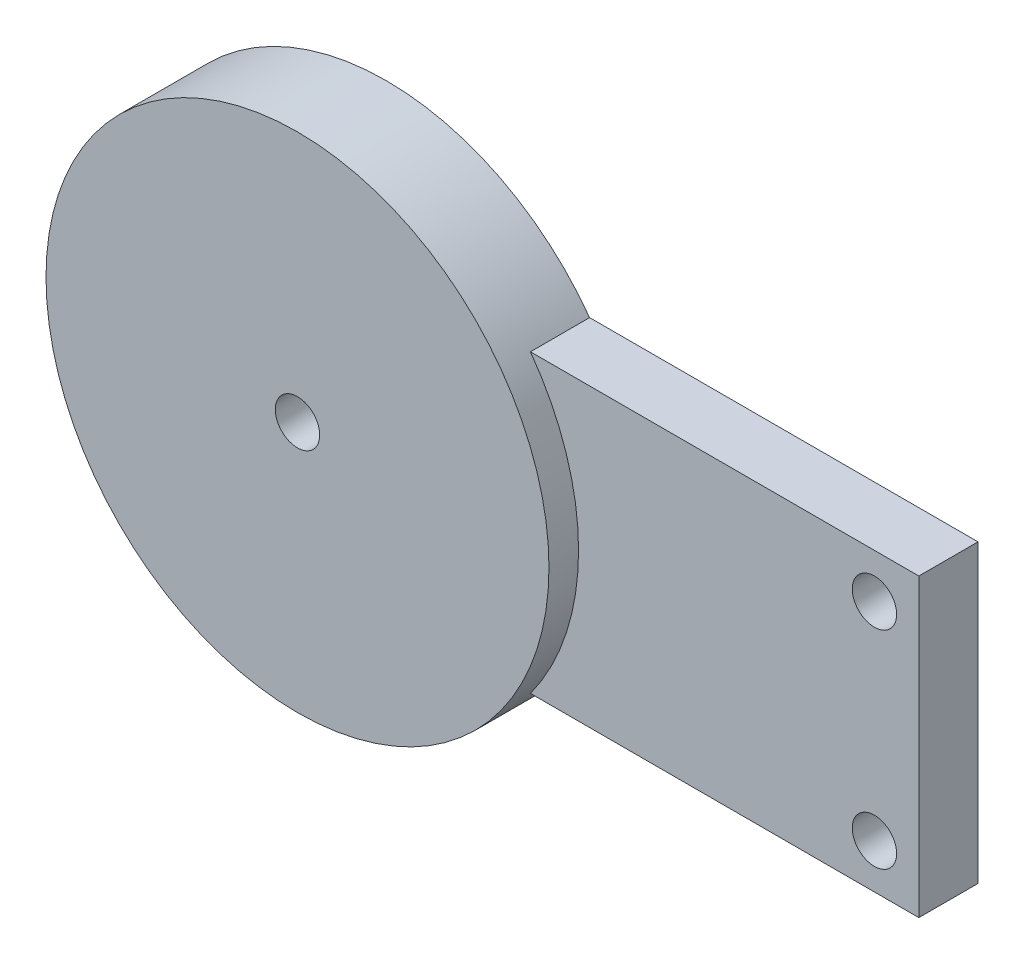
SolidWorks part; units mm, degrees
ref_plane "Plano frontal" through (0, 0, 0) normal (0, 0, 1) x (1, 0, 0)
ref_plane "Plano superior" through (0, 0, 0) normal (0, 1, 0) x (1, 0, 0)
ref_plane "Plano direito" through (0, 0, 0) normal (1, 0, 0) x (0, 0, -1)
sketch "Sketch1" plane through (0, 0, 0) normal (0, 0, 1) x (1, 0, 0)
  line L1 (-20, -10) -> (20, -10)
  line L2 (-20, -10) -> (-20, 10)
  line L3 (-20, 10) -> (20, 10)
  line L4 (20, -10) -> (20, 10)
  line L5 (-20, -10) -> (20, 10) construction
  line L6 (-20, 10) -> (20, -10) construction
  point P0 (0, 0)
  dimension "D1" = 40
  dimension "D2" = 20
extrude "Boss-Extrude1" add sketch "Sketch1" along normal mid plane 4
sketch "Sketch6" plane through (0, 0, 2) normal (0, 0, 1) x (1, 0, 0)
  line L0 (-20, 10) -> (-20, -10) construction
  circle A0 centre (-20, 0) radius 17
  dimension "D1" = 34
extrude "Boss-Extrude2" add sketch "Sketch6" against normal up to surface (4 mm away) and the other way blind 2 up to face at (0, 0, -2)
sketch "Sketch7" plane through (0, 0, -2) normal (0, 0, -1) x (-1, 0, 0)
  line L0 (20, 4.325) -> (33.5, 2.5)
  line L1 (20, -4.325) -> (33.5, -2.5)
  circle A0 centre (20, 0) radius 4.325
  circle A1 centre (33.5, 0) radius 2.5
  dimension "D1" = 8.65
  dimension "D2" = 5
  dimension "D3" = 13.5
extrude "Cut-Extrude3" cut sketch "Sketch7" against normal blind 3 contours L0 A0 L1 | A1 L0 A0 L1 | A1 region at (-19.9994, 0, -2) region at (-27.3678, 0, -2) region at (-33.5, 0, -2)
pattern_circular "CirPattern1" count 6 every 60 about axis through (-20, 0, 1) along (0, 0, -1) of "Cut-Extrude3"
fillet "Fillet3" radius 1 6 edges at (-13.9301, -3.5044, -0.5) (-26.0699, 3.5044, -0.5) (-20, 7.0089, -0.5) (-13.9301, 3.5044, -0.5) (-20, -7.0089, -0.5) (-26.0699, -3.5044, -0.5)
sketch "Sketch8" plane through (0, 0, 4) normal (0, 0, 1) x (1, 0, 0)
  circle A0 centre (-20, 0) radius 1.5
  dimension "D1" = 3
extrude "Cut-Extrude4" cut sketch "Sketch8" against normal up to next
sketch "Sketch9" plane through (0, 0, 2) normal (0, 0, 1) x (1, 0, 0)
  line L0 (20, -10) -> (20, 10) construction
  line L1 (20, 10) -> (-6.2523, 10) construction
  line L2 (-6.2523, -10) -> (20, -10) construction
  circle A0 centre (17, 7) radius 1.5
  circle A1 centre (17, -7) radius 1.5
  dimension "D1" = 3
  dimension "D2" = 3
  dimension "D3" = 3
  dimension "D4" = 3
  dimension "D5" = 3
  dimension "D6" = 3
extrude "Cut-Extrude5" cut sketch "Sketch9" against normal up to next
equation "\"D2@Sketch9\"=\"D1@Sketch9\""
equation "\"D5@Sketch9\"=\"D3@Sketch9\""
equation "\"D6@Sketch9\"=\"D4@Sketch9\""
